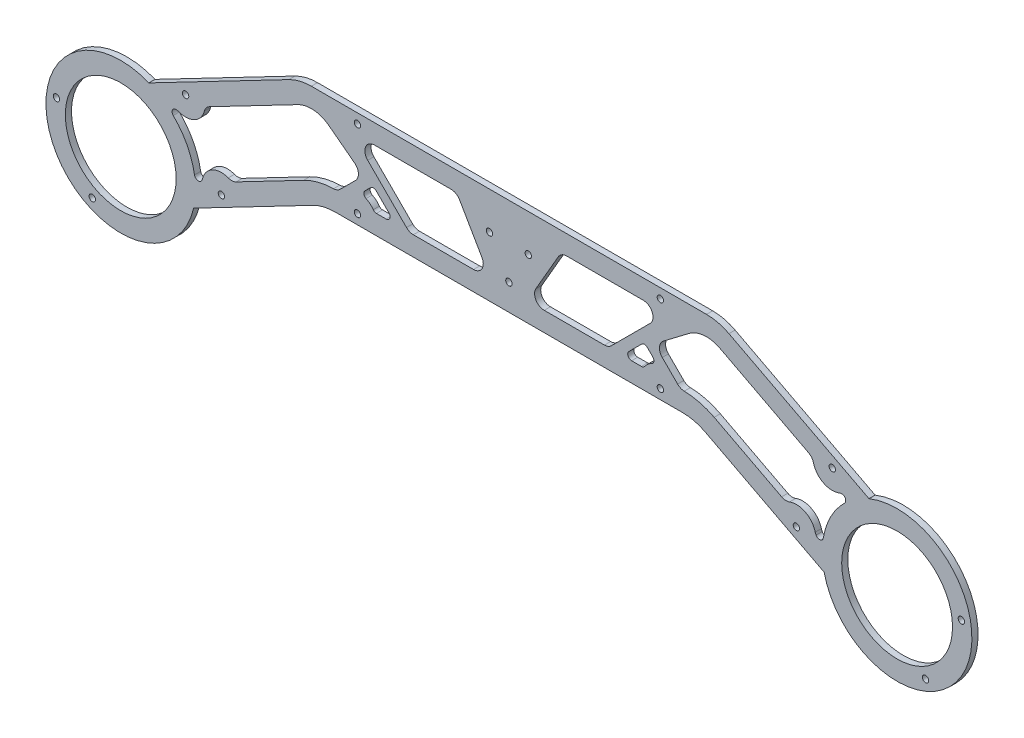
SolidWorks part; units mm, degrees
note: The reader was unsure of these and kept them because the rebuilt part matched: shared geometry of "Sketch5<2>".
material "6061-T6 (SS)"
ref_plane "Front Plane" through (0, 0, 0) normal (0, 0, 1) x (1, 0, 0)
ref_plane "Top Plane" through (0, 0, 0) normal (0, 1, 0) x (1, 0, 0)
ref_plane "Right Plane" through (0, 0, 0) normal (1, 0, 0) x (0, 0, -1)
sketch "Sketch1" plane through (0, 0, 0) normal (0, 0, 1) x (1, 0, 0)
  line L0 (-200, -104.1134) -> (0, 0) construction
  line L1 (0, 0) -> (200, -104.1134) construction
  line L2 (-221.4586, -97.3475) -> (-193.2341, -82.6548) construction
  line L3 (-113.3558, -30.8247) -> (-235.4371, -94.3763)
  line L4 (-237.5634, -101.1201) -> (-219.0935, -136.6005)
  line L5 (-212.3497, -138.7268) -> (-101.1208, -80.8247)
  line L6 (-101.8121, -28) -> (101.8121, -28)
  line L7 (0, -28) -> (0, -78) construction
  line L8 (89.5771, -78) -> (-89.5771, -78)
  line L9 (113.3558, -30.8247) -> (235.4371, -94.3763)
  line L10 (237.5634, -101.1201) -> (219.0935, -136.6005)
  line L11 (212.3497, -138.7268) -> (101.1208, -80.8247)
  circle A1 centre (-200, -104.1134) radius 16.05
  circle A2 centre (-221.4586, -97.3475) radius 1.65
  circle A3 centre (-193.2341, -82.6548) radius 1.65
  circle A4 centre (-178.5414, -110.8793) radius 1.65
  circle A5 centre (-206.7659, -125.572) radius 1.65
  arc A6 (-235.4371, -94.3763) -> (-237.5634, -101.1201) centre (-233.1284, -98.8113) ccw
  arc A7 (-219.0935, -136.6005) -> (-212.3497, -138.7268) centre (-214.6584, -134.2918) ccw
  circle A8 centre (0, 0) radius 25 construction
  circle A11 centre (-200, -104.1134) radius 33.55 construction
  circle A12 centre (206.7659, -125.572) radius 1.65
  circle A13 centre (221.4586, -97.3475) radius 1.65
  circle A14 centre (193.2341, -82.6548) radius 1.65
  circle A15 centre (178.5414, -110.8793) radius 1.65
  circle A16 centre (200, -104.1134) radius 16.05
  arc A17 (235.4371, -94.3763) -> (237.5634, -101.1201) centre (233.1284, -98.8113) cw
  arc A18 (219.0935, -136.6005) -> (212.3497, -138.7268) centre (214.6584, -134.2918) cw
  circle A19 centre (-10, -47.2265) radius 1.65
  circle A20 centre (10, -47.2265) radius 1.65
  circle A21 centre (0, -64.547) radius 1.65
  arc A22 (101.1208, -80.8247) -> (89.5771, -78) centre (89.5771, -103) ccw
  arc A23 (113.3558, -30.8247) -> (101.8121, -28) centre (101.8121, -53) ccw
  arc A24 (-113.3558, -30.8247) -> (-101.8121, -28) centre (-101.8121, -53) cw
  arc A25 (-101.1208, -80.8247) -> (-89.5771, -78) centre (-89.5771, -103) cw
  point P17 (-200, -104.1134)
  point P27 (0, -53)
  point P28 (0, -25)
  point P53 (0, -53)
  point P54 (95.6946, -78)
  point P57 (107.9295, -28)
  point P60 (-107.9295, -28)
  point P63 (-95.6946, -78)
  dimension "D1" = 400
  dimension "D3" = 32.1
  dimension "D5" = 3.3
  dimension "D7" = 50
  dimension "D10" = 5
  dimension "D11" = 3.3
  dimension "D12" = 67.1
  dimension "D14" = 3
  dimension "D16" = 25
  dimension "D2" = 125
  dimension "D6" = 45
  dimension "D8" = 3
  dimension "D9" = 50
  dimension "D13" = 50
  dimension "D15" = 20
  dimension "D4" = 4
extrude "Base" add sketch "Sketch1" along normal blind 3.175
sketch "Sketch3" plane through (0, 0, 3.175) normal (0, 0, 1) x (1, 0, 0)
  line L1 (-89.5771, -78) -> (89.5771, -78) construction
  line L2 (-228.3285, -118.8603) -> (-185.7635, -96.7023) construction
  line L3 (101.8121, -28) -> (-101.8121, -28) construction
  line L4 (-237.5634, -101.1201) -> (-219.0935, -136.6005) construction
  line L5 (0, -28) -> (0, -78) construction
  circle A0 centre (-214.6584, -134.2918) radius 1.65
  circle A1 centre (-148.1326, -99.6606) radius 1.65
  circle A2 centre (-78.0312, -73) radius 1.65
  circle A3 centre (-78.0312, -33) radius 1.65
  circle A4 centre (-200, -104.1134) radius 16.05 construction
  circle A5 centre (-166.6026, -64.1802) radius 1.65
  circle A6 centre (-233.1284, -98.8113) radius 1.65
  circle A7 centre (233.1284, -98.8113) radius 1.65
  circle A8 centre (166.6026, -64.1802) radius 1.65
  circle A9 centre (78.0312, -33) radius 1.65
  circle A10 centre (78.0312, -73) radius 1.65
  circle A11 centre (148.1326, -99.6606) radius 1.65
  circle A12 centre (214.6584, -134.2918) radius 1.65
  dimension "D1" = 3.3
  dimension "D3" = 75
  dimension "D6" = 5
  dimension "D4" = 5
  dimension "D5" = 75
  dimension "D2" = 2
extrude "Strut Holes" cut sketch "Sketch3" against normal through all
sketch "Sketch4" plane through (0, 0, 0) normal (0, 0, -1) x (-1, 0, 0)
  line L0 (-166.7326, -103.7062) -> (-160.3585, -100.3881)
  line L1 (-101.1208, -80.8247) -> (-212.3497, -138.7268) construction
  line L2 (-140.5243, -90.063) -> (-105.7383, -71.9546)
  line L3 (-86.9223, -66.5452) -> (-79.0095, -58.6325)
  line L4 (-79.5169, -51.1182) -> (-92.7277, -41.0638)
  line L5 (-180.585, -77.0959) -> (-174.2109, -73.7777)
  line L6 (-235.4371, -94.3763) -> (-113.3558, -30.8247) construction
  line L7 (-154.3768, -63.4527) -> (-108.7383, -39.6948)
  line L8 (89.5771, -78) -> (-89.5771, -78) construction
  line L9 (-68.2844, -68) -> (-63.1994, -68)
  line L10 (-61.7852, -64.5858) -> (-68.4242, -57.9467)
  line L11 (-71.2527, -57.9467) -> (-74.1321, -60.8262)
  line L12 (-25.4306, -40.5) -> (-13.8835, -60.5)
  line L13 (-18.2137, -68) -> (-49.2288, -68)
  line L14 (-52.7643, -66.5355) -> (-72.7643, -46.5355)
  line L15 (-69.2288, -38) -> (-29.7607, -38)
  line L16 (-101.8121, -28) -> (101.8121, -28) construction
  line L17 (0, -28) -> (0, -78) construction
  line L18 (52.7643, -66.5355) -> (72.7643, -46.5355)
  line L19 (18.2137, -68) -> (49.2288, -68)
  line L20 (25.4306, -40.5) -> (13.8835, -60.5)
  line L21 (69.2288, -38) -> (29.7607, -38)
  line L22 (68.2844, -68) -> (63.1994, -68)
  line L23 (61.7852, -64.5858) -> (68.4242, -57.9467)
  line L24 (71.2527, -57.9467) -> (74.1321, -60.8262)
  line L25 (154.3768, -63.4527) -> (108.7383, -39.6948)
  line L26 (180.585, -77.0959) -> (174.2109, -73.7777)
  line L27 (166.7326, -103.7062) -> (160.3585, -100.3881)
  line L28 (140.5243, -90.063) -> (105.7383, -71.9546)
  line L29 (86.9223, -66.5452) -> (79.0095, -58.6325)
  line L30 (79.5169, -51.1182) -> (92.7277, -41.0638)
  arc A0 (-182.112, -88.1128) -> (-176.6329, -98.638) centre (-200, -104.1134) cw
  arc A1 (-174.0237, -101.958) -> (-172.208, -103.1405) centre (-178.5414, -110.8793) cw
  arc A2 (-183.3349, -84.0711) -> (-183.2622, -81.9056) centre (-193.2341, -82.6548) ccw
  arc A3 (-157.8223, -97.1889) -> (-144.5996, -90.3055) centre (-148.1326, -99.6606) cw
  arc A4 (-105.7383, -71.9546) -> (-90.3477, -68.0085) centre (-89.5771, -103) cw
  arc A5 (-89.5771, -78) -> (-101.1208, -80.8247) centre (-89.5771, -103) ccw construction
  arc A6 (-170.1356, -73.5353) -> (-156.9129, -66.6519) centre (-166.6026, -64.1802) ccw
  arc A7 (-108.7383, -39.6948) -> (-92.7277, -41.0638) centre (-101.8121, -53) cw
  arc A8 (-101.8121, -28) -> (-113.3558, -30.8247) centre (-101.8121, -53) ccw construction
  arc A9 (-69.9089, -67.1667) -> (-73.6035, -64.0337) centre (-78.0312, -73) ccw
  circle A10 centre (-10, -47.2265) radius 10 construction
  circle A11 centre (0, -64.547) radius 10 construction
  arc A12 (-156.9129, -66.6519) -> (-154.3768, -63.4527) centre (-152.068, -67.8878) cw
  arc A13 (-174.2109, -73.7777) -> (-170.1356, -73.5353) centre (-171.9022, -78.2128) cw
  arc A14 (-183.2622, -81.9056) -> (-180.585, -77.0959) centre (-178.2763, -81.5309) cw
  arc A15 (-182.112, -88.1128) -> (-183.3349, -84.0711) centre (-178.3853, -84.7793) cw
  arc A16 (-176.6329, -98.638) -> (-174.0237, -101.958) centre (-171.7648, -97.4973) ccw
  arc A17 (-172.208, -103.1405) -> (-166.7326, -103.7062) centre (-169.0413, -99.2712) ccw
  arc A18 (-160.3585, -100.3881) -> (-157.8223, -97.1889) centre (-162.6672, -95.953) ccw
  arc A19 (-144.5996, -90.3055) -> (-140.5243, -90.063) centre (-142.833, -85.628) ccw
  arc A20 (-79.0095, -58.6325) -> (-79.5169, -51.1182) centre (-82.545, -55.0969) ccw
  arc A21 (-90.3477, -68.0085) -> (-86.9223, -66.5452) centre (-90.4578, -63.0097) ccw
  arc A22 (-49.2288, -68) -> (-52.7643, -66.5355) centre (-49.2288, -63) cw
  arc A23 (-25.4306, -40.5) -> (-29.7607, -38) centre (-29.7607, -43) ccw
  arc A24 (-13.8835, -60.5) -> (-18.2137, -68) centre (-18.2137, -63) cw
  arc A25 (-72.7643, -46.5355) -> (-69.2288, -38) centre (-69.2288, -43) cw
  arc A26 (-68.4242, -57.9467) -> (-71.2527, -57.9467) centre (-69.8385, -59.3609) ccw
  arc A27 (-68.2844, -68) -> (-69.9089, -67.1667) centre (-68.2844, -66) cw
  arc A28 (-74.1321, -60.8262) -> (-73.6035, -64.0337) centre (-72.7179, -62.2404) ccw
  arc A29 (-63.1994, -68) -> (-61.7852, -64.5858) centre (-63.1994, -66) ccw
  arc A30 (49.2288, -68) -> (52.7643, -66.5355) centre (49.2288, -63) ccw
  arc A31 (13.8835, -60.5) -> (18.2137, -68) centre (18.2137, -63) ccw
  arc A32 (25.4306, -40.5) -> (29.7607, -38) centre (29.7607, -43) cw
  arc A33 (72.7643, -46.5355) -> (69.2288, -38) centre (69.2288, -43) ccw
  arc A34 (63.1994, -68) -> (61.7852, -64.5858) centre (63.1994, -66) cw
  arc A35 (68.4242, -57.9467) -> (71.2527, -57.9467) centre (69.8385, -59.3609) cw
  arc A36 (68.2844, -68) -> (69.9089, -67.1667) centre (68.2844, -66) ccw
  arc A37 (74.1321, -60.8262) -> (73.6035, -64.0337) centre (72.7179, -62.2404) cw
  arc A38 (69.9089, -67.1667) -> (73.6035, -64.0337) centre (78.0312, -73) cw
  arc A39 (156.9129, -66.6519) -> (154.3768, -63.4527) centre (152.068, -67.8878) ccw
  arc A40 (170.1356, -73.5353) -> (156.9129, -66.6519) centre (166.6026, -64.1802) cw
  arc A41 (174.2109, -73.7777) -> (170.1356, -73.5353) centre (171.9022, -78.2128) ccw
  arc A42 (183.2622, -81.9056) -> (180.585, -77.0959) centre (178.2763, -81.5309) ccw
  arc A43 (183.3349, -84.0711) -> (183.2622, -81.9056) centre (193.2341, -82.6548) cw
  arc A44 (182.112, -88.1128) -> (183.3349, -84.0711) centre (178.3853, -84.7793) ccw
  arc A45 (182.112, -88.1128) -> (176.6329, -98.638) centre (200, -104.1134) ccw
  arc A46 (176.6329, -98.638) -> (174.0237, -101.958) centre (171.7648, -97.4973) cw
  arc A47 (174.0237, -101.958) -> (172.208, -103.1405) centre (178.5414, -110.8793) ccw
  arc A48 (172.208, -103.1405) -> (166.7326, -103.7062) centre (169.0413, -99.2712) cw
  arc A49 (160.3585, -100.3881) -> (157.8223, -97.1889) centre (162.6672, -95.953) cw
  arc A50 (157.8223, -97.1889) -> (144.5996, -90.3055) centre (148.1326, -99.6606) ccw
  arc A51 (144.5996, -90.3055) -> (140.5243, -90.063) centre (142.833, -85.628) cw
  arc A52 (105.7383, -71.9546) -> (90.3477, -68.0085) centre (89.5771, -103) ccw
  arc A53 (90.3477, -68.0085) -> (86.9223, -66.5452) centre (90.4578, -63.0097) cw
  arc A54 (79.0095, -58.6325) -> (79.5169, -51.1182) centre (82.545, -55.0969) cw
  arc A55 (108.7383, -39.6948) -> (92.7277, -41.0638) centre (101.8121, -53) ccw
  point P75 (-74.9619, -54.5849)
  point P78 (-88.3969, -68.0199)
  point P91 (-69.3709, -68)
  point P96 (-58.3709, -68)
  dimension "D1" = 24
  dimension "D2" = 10
  dimension "D4" = 10
  dimension "D5" = 11.5
  dimension "D6" = 5
  dimension "D10" = 2.2457
  dimension "D15" = 5
  dimension "D16" = 5
  dimension "D17" = 2
  dimension "D3" = 10
  dimension "45" = 45
  dimension "D7" = 11.5
  dimension "D8" = 10
  dimension "D9" = 45
  dimension "D11" = 19
  dimension "D12" = 11
  dimension "D13" = 10
  dimension "D14" = 10
extrude "Lightening Holes" cut sketch "Sketch4" against normal through all
sketch "Sketch5" plane through (0, 0, 0) normal (0, 0, -1) x (-1, 0, 0)
  circle A0 centre (-200, -104.1134) radius 28.55
  circle A1 centre (-200, -104.1134) radius 38.55
  circle A2 centre (-233.1284, -98.8113) radius 1.65 construction
  circle A3 centre (-214.6584, -134.2918) radius 1.65 construction
  circle A4 centre (-233.1284, -98.8113) radius 1.65
  circle A5 centre (-214.6584, -134.2918) radius 1.65
  dimension "D1" = 57.1
  dimension "D2" = 10
extrude "Inner Mod Boss" add sketch "Sketch5" against normal up to surface (3.175 mm away) up to face at (144.3427, -77.7595, 3.175)
extrude "Inner Mod Cut" cut sketch "Sketch5<2>" against normal through all contours A0
sketch "Sketch5<2>" plane through (0, 0, 0) normal (0, 0, -1) x (-1, 0, 0) same geometry as "Sketch5"
fillet "Fillet1" radius 2 4 edges at (174.8188, -74.0942, 3.175) (174.2109, -73.7777, 1.5875) (174.8188, -74.0942, 0) (175.4267, -74.4106, 1.5875)
fillet "Fillet2" radius 2 4 edges at (160.3585, -100.3881, 1.5875) (160.9663, -100.7045, 0) (160.9663, -100.7045, 3.175) (161.5742, -101.021, 1.5875)
mirror "Mirror1" about plane through (0, 0, 0) normal (1, 0, 0) of "Inner Mod Boss", "Inner Mod Cut"
fillet "Fillet3" radius 2 4 edges at (-174.8188, -74.0942, 0) (-174.8188, -74.0942, 3.175) (-175.4267, -74.4106, 1.5875) (-174.2109, -73.7777, 1.5875)
fillet "Fillet4" radius 2 4 edges at (-161.5742, -101.021, 1.5875) (-160.9663, -100.7045, 3.175) (-160.3585, -100.3881, 1.5875) (-160.9663, -100.7045, 0)
